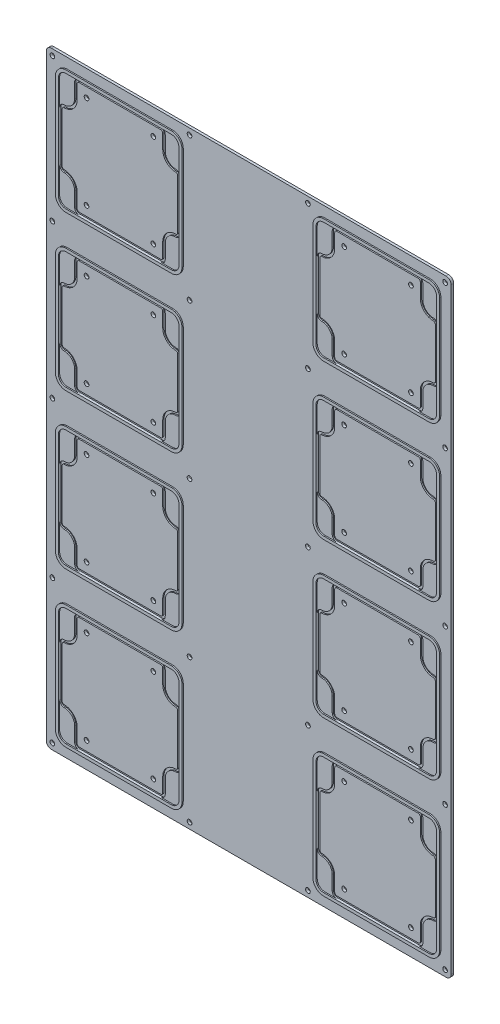
SolidWorks part; units mm, degrees
ref_plane "Front Plane" through (0, 0, 0) normal (0, 0, 1) x (1, 0, 0)
ref_plane "Top Plane" through (0, 0, 0) normal (0, 1, 0) x (1, 0, 0)
ref_plane "Right Plane" through (0, 0, 0) normal (1, 0, 0) x (0, 0, -1)
sketch "Sketch1" plane through (0, 0, 0) normal (0, 0, 1) x (1, 0, 0)
  line L1 (0, 0) -> (254, 0)
  line L2 (0, 0) -> (0, 381)
  line L3 (0, 381) -> (254, 381)
  line L4 (254, 0) -> (254, 381)
  dimension "D1" = 381
  dimension "D2" = 254
extrude "Boss-Extrude1" add sketch "Sketch1" along normal blind 1.5875
sketch "Sketch2" plane through (0, 0, 1.5875) normal (0, 0, 1) x (1, 0, 0)
  line L0 (89.8652, 377.19) -> (89.8652, 3.81) construction
  line L1 (0, 381) -> (254, 381) construction
  line L2 (127, 381) -> (127, 377.19) construction
  line L3 (3.81, 377.19) -> (250.19, 377.19) construction
  line L5 (164.1348, 377.19) -> (164.1348, 3.81) construction
  line L6 (3.81, 377.19) -> (3.81, 3.81) construction
  line L7 (3.81, 3.81) -> (250.19, 3.81) construction
  line L8 (250.19, 3.81) -> (250.19, 377.19) construction
  line L9 (3.81, 190.5) -> (250.19, 190.5) construction
  line L10 (3.81, 287.3756) -> (250.19, 287.3756) construction
  line L11 (3.81, 93.6244) -> (250.19, 93.6244) construction
  line L12 (0, 381) -> (0, 0) construction
  line L13 (0, 190.5) -> (3.81, 190.5) construction
  circle A0 centre (3.81, 377.19) radius 1.4732
  circle A1 centre (89.8652, 377.19) radius 1.4732
  circle A2 centre (164.1348, 377.19) radius 1.4732
  circle A3 centre (250.19, 377.19) radius 1.4732
  circle A4 centre (164.1348, 287.3755) radius 1.4732
  circle A5 centre (3.81, 287.3756) radius 1.4732
  circle A6 centre (250.19, 287.3756) radius 1.4732
  circle A7 centre (89.8652, 287.3756) radius 1.4732
  circle A8 centre (164.1348, 190.5) radius 1.4732
  circle A9 centre (3.81, 191.135) radius 1.4732
  circle A10 centre (250.19, 190.5) radius 1.4732
  circle A11 centre (89.8652, 190.5) radius 1.4732
  circle A12 centre (164.1348, 93.6244) radius 1.4732
  circle A13 centre (3.81, 93.6244) radius 1.4732
  circle A14 centre (250.19, 93.6244) radius 1.4732
  circle A15 centre (89.8652, 93.6244) radius 1.4732
  circle A16 centre (164.1348, 3.81) radius 1.4732
  circle A17 centre (3.81, 3.81) radius 1.4732
  circle A18 centre (250.19, 3.81) radius 1.4732
  circle A19 centre (89.8652, 3.81) radius 1.4732
  dimension "D6" = 2.9464
  dimension "D23" = 0
  dimension "D24" = 0
  dimension "D25" = 0
  dimension "D28" = 0
  dimension "D29" = 0
  dimension "D30" = 0
  dimension "D31" = 0
  dimension "D32" = 86.0552
  dimension "D1" = 246.38
  dimension "D3" = 373.38
  dimension "D4" = 96.8756
  dimension "D5" = 96.8756
  dimension "D7" = 86.0552
  dimension "D8" = 86.0552
  dimension "D9" = 0
  dimension "D10" = 0
  dimension "D11" = 0
  dimension "D12" = 86.0552
  dimension "D13" = 0
  dimension "D14" = 0
  dimension "D15" = 0
  dimension "D16" = 0
  dimension "D17" = 0
  dimension "D18" = 0
  dimension "D19" = 0
  dimension "D20" = 0
  dimension "D21" = 0
  dimension "D22" = 0
  dimension "D26" = 0
  dimension "D27" = 0
extrude "Cut-Extrude1" cut sketch "Sketch2" against normal through all
fillet "Fillet1" radius 3.175 4 edges at (254, 0, 0.7937) (0, 0, 0.7937) (254, 381, 0.7937) (0, 381, 0.7937)
sketch "Sketch3" plane through (0, 0, 1.5875) normal (0, 0, 1) x (1, 0, 0)
  line L0 (9.9695, 45.1866) -> (46.2026, 45.1866) construction
  line L1 (46.2026, 45.1866) -> (46.2026, 9.9695) construction
  line L2 (81.2038, 28.3591) -> (82.4357, 28.3591) construction
  line L3 (82.4357, 29.591) -> (82.4357, 60.7822)
  line L4 (73.0377, 11.2014) -> (73.0377, 20.193)
  line L5 (81.2038, 62.0141) -> (82.4357, 62.0141) construction
  line L6 (71.8058, 9.9695) -> (20.5994, 9.9695)
  line L7 (19.3675, 11.2014) -> (19.3675, 20.193)
  line L8 (11.2014, 28.3591) -> (9.9695, 28.3591) construction
  line L9 (9.9695, 29.591) -> (9.9695, 60.7822)
  line L10 (73.0377, 79.1718) -> (73.0377, 70.1802)
  line L11 (71.8058, 80.4037) -> (20.5994, 80.4037)
  line L12 (3.175, 0) -> (250.825, 0) construction
  line L13 (0, 377.825) -> (0, 3.175) construction
  line L14 (11.2014, 62.0141) -> (9.9695, 62.0141) construction
  line L15 (19.3675, 79.1718) -> (19.3675, 70.1802)
  line L16 (17.78, 79.1718) -> (17.78, 70.1802)
  line L17 (8.382, 29.591) -> (8.382, 60.7822)
  line L18 (17.78, 11.2014) -> (17.78, 20.193)
  line L19 (71.8058, 8.382) -> (20.5994, 8.382)
  line L20 (74.6252, 11.2014) -> (74.6252, 20.193)
  line L21 (84.0232, 29.591) -> (84.0232, 60.7822)
  line L22 (74.6252, 79.1718) -> (74.6252, 70.1802)
  line L23 (71.8058, 81.9912) -> (20.5994, 81.9912)
  arc A0 (19.3675, 20.193) -> (11.2014, 28.3591) centre (11.2014, 20.193) ccw
  arc A1 (9.9695, 29.591) -> (11.2014, 28.3591) centre (11.2014, 29.591) ccw
  arc A2 (19.3675, 11.2014) -> (20.5994, 9.9695) centre (20.5994, 11.2014) ccw
  arc A3 (73.0377, 11.2014) -> (71.8058, 9.9695) centre (71.8058, 11.2014) cw
  arc A4 (82.4357, 29.591) -> (81.2038, 28.3591) centre (81.2038, 29.591) cw
  arc A5 (73.0377, 20.193) -> (81.2038, 28.3591) centre (81.2038, 20.193) cw
  arc A6 (73.0377, 70.1802) -> (81.2038, 62.0141) centre (81.2038, 70.1802) ccw
  arc A7 (82.4357, 60.7822) -> (81.2038, 62.0141) centre (81.2038, 60.7822) ccw
  arc A8 (73.0377, 79.1718) -> (71.8058, 80.4037) centre (71.8058, 79.1718) ccw
  arc A9 (19.3675, 79.1718) -> (20.5994, 80.4037) centre (20.5994, 79.1718) cw
  arc A10 (9.9695, 60.7822) -> (11.2014, 62.0141) centre (11.2014, 60.7822) cw
  arc A11 (19.3675, 70.1802) -> (11.2014, 62.0141) centre (11.2014, 70.1802) cw
  arc A12 (17.78, 70.1802) -> (11.2014, 63.6016) centre (11.2014, 70.1802) cw
  arc A13 (8.382, 60.7822) -> (11.2014, 63.6016) centre (11.2014, 60.7822) cw
  arc A14 (8.382, 29.591) -> (11.2014, 26.7716) centre (11.2014, 29.591) ccw
  arc A15 (17.78, 20.193) -> (11.2014, 26.7716) centre (11.2014, 20.193) ccw
  arc A16 (17.78, 11.2014) -> (20.5994, 8.382) centre (20.5994, 11.2014) ccw
  arc A17 (74.6252, 11.2014) -> (71.8058, 8.382) centre (71.8058, 11.2014) cw
  arc A18 (74.6252, 20.193) -> (81.2038, 26.7716) centre (81.2038, 20.193) cw
  arc A19 (84.0232, 29.591) -> (81.2038, 26.7716) centre (81.2038, 29.591) cw
  arc A20 (84.0232, 60.7822) -> (81.2038, 63.6016) centre (81.2038, 60.7822) ccw
  arc A21 (74.6252, 70.1802) -> (81.2038, 63.6016) centre (81.2038, 70.1802) ccw
  arc A22 (74.6252, 79.1718) -> (71.8058, 81.9912) centre (71.8058, 79.1718) ccw
  arc A23 (17.78, 79.1718) -> (20.5994, 81.9912) centre (20.5994, 79.1718) cw
  point P35 (82.4357, 45.1866)
  dimension "D6" = 8.1661
  dimension "D7" = 2.4638
  dimension "D8" = 1.2319
  dimension "D1" = 9.9695
  dimension "D2" = 9.9695
  dimension "D3" = 19.3675
  dimension "D4" = 28.3591
  dimension "D5" = 45.1866
  dimension "D10" = 46.2026
  dimension "D9" = 1.5875
extrude "Cut-Extrude2" cut sketch "Sketch3" against normal blind 0.7937
sketch "Sketch4" plane through (0, 0, 1.5875) normal (0, 0, 1) x (1, 0, 0)
  line L0 (8.382, 60.7822) -> (8.382, 77.2287)
  line L1 (13.1445, 81.9912) -> (20.5994, 81.9912)
  line L2 (20.5994, 81.9912) -> (79.2607, 81.9912)
  line L3 (84.0232, 77.2287) -> (84.0232, 13.1445)
  line L4 (79.2607, 8.382) -> (13.1445, 8.382)
  line L5 (8.382, 13.1445) -> (8.382, 60.7822)
  line L6 (6.477, 60.7822) -> (6.477, 77.2287)
  line L7 (13.1445, 83.8962) -> (20.5994, 83.8962)
  line L8 (20.5994, 83.8962) -> (79.2607, 83.8962)
  line L9 (85.9282, 77.2287) -> (85.9282, 13.1445)
  line L10 (79.2607, 6.477) -> (13.1445, 6.477)
  line L11 (6.477, 13.1445) -> (6.477, 60.7822)
  arc A0 (13.1445, 81.9912) -> (8.382, 77.2287) centre (13.1445, 77.2287) ccw
  arc A1 (79.2607, 81.9912) -> (84.0232, 77.2287) centre (79.2607, 77.2287) cw
  arc A2 (84.0232, 13.1445) -> (79.2607, 8.382) centre (79.2607, 13.1445) cw
  arc A3 (8.382, 13.1445) -> (13.1445, 8.382) centre (13.1445, 13.1445) ccw
  arc A4 (13.1445, 83.8962) -> (6.477, 77.2287) centre (13.1445, 77.2287) ccw
  arc A5 (79.2607, 83.8962) -> (85.9282, 77.2287) centre (79.2607, 77.2287) cw
  arc A6 (85.9282, 13.1445) -> (79.2607, 6.477) centre (79.2607, 13.1445) cw
  arc A7 (6.477, 13.1445) -> (13.1445, 6.477) centre (13.1445, 13.1445) ccw
  dimension "D1" = 4.7625
  dimension "D2" = 1.905
extrude "Boss-Extrude2" add sketch "Sketch4" along normal blind 0.7937
sketch "Sketch5" plane through (0, 0, 1.5875) normal (0, 0, 1) x (1, 0, 0)
  line L0 (9.9695, 45.1866) -> (82.4357, 45.1866) construction
  line L1 (9.9695, 60.7822) -> (9.9695, 29.591) construction
  line L2 (82.4357, 29.591) -> (82.4357, 60.7822) construction
  line L3 (82.4357, 45.1866) -> (46.2026, 45.1866) construction
  line L4 (46.2026, 45.1866) -> (46.2026, 80.4037) construction
  line L5 (71.8058, 80.4037) -> (20.5994, 80.4037) construction
  circle A0 centre (25.2476, 74.3966) radius 1.4732
  circle A1 centre (67.1576, 74.3966) radius 1.4732
  circle A2 centre (67.1576, 15.9766) radius 1.4732
  circle A3 centre (25.2476, 15.9766) radius 1.4732
  dimension "D1" = 2.9464
  dimension "D2" = 20.955
  dimension "D3" = 29.21
extrude "Cut-Extrude3" cut sketch "Sketch5" against normal through all
pattern_linear "LPattern1" count 4 spacing 96.8756 along (0, 1, 0) count 2 spacing 161.5948 along (1, 0, 0) of "Cut-Extrude2", "Boss-Extrude2", "Cut-Extrude3"
